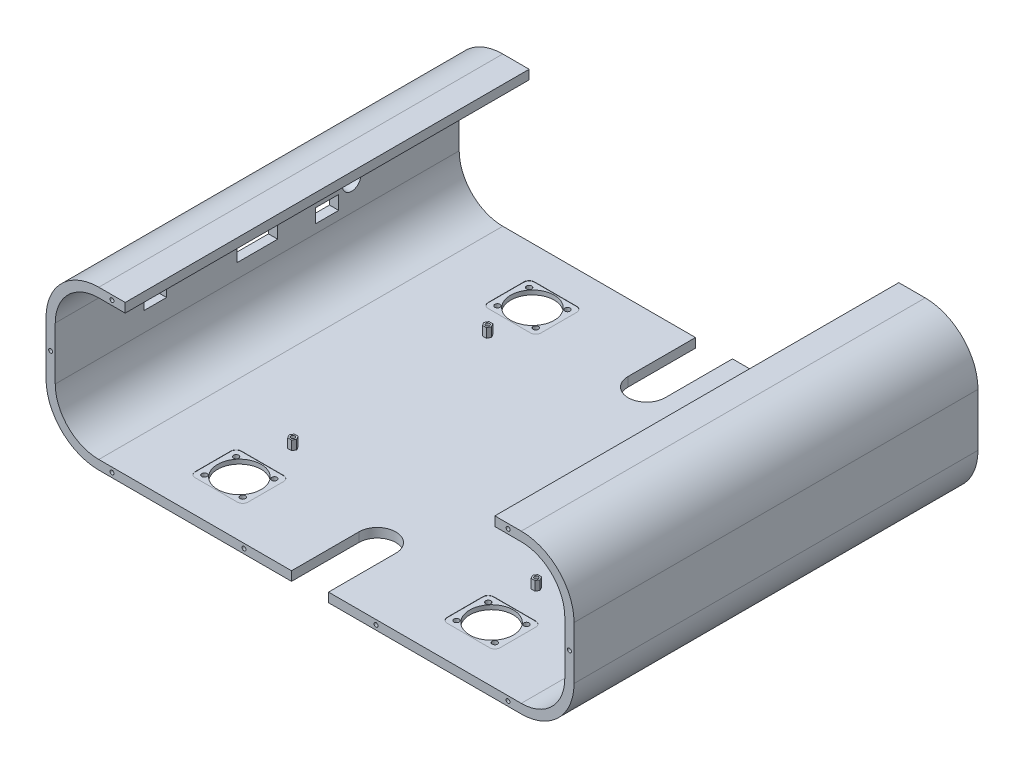
SolidWorks part; units mm, degrees
material "6061-T6 (SS)"
ref_plane "Front Plane" through (0, 0, 0) normal (0, 0, 1) x (1, 0, 0)
ref_plane "Top Plane" through (0, 0, 0) normal (0, 1, 0) x (1, 0, 0)
ref_plane "Right Plane" through (0, 0, 0) normal (1, 0, 0) x (0, 0, -1)
sketch "Sketch1" plane through (0, 0, 0) normal (0, 1, 0) x (1, 0, 0)
  line L1 (-200, -153) -> (200, -153)
  line L2 (-200, -153) -> (-200, 153)
  line L3 (-200, 153) -> (200, 153)
  line L4 (200, -153) -> (200, 153)
  line L5 (-200, -153) -> (200, 153) construction
  line L6 (-200, 153) -> (200, -153) construction
  point P0 (0, 0)
  dimension "D1" = 400
  dimension "D2" = 306
extrude "Boss-Extrude1" add sketch "Sketch1" along normal blind 7
sketch "Sketch5" plane through (0, 0, 153) normal (0, 0, 1) x (1, 0, 0)
  line L0 (0, 0) -> (0, 120) construction
  line L1 (-140, 0) -> (-160, 0)
  line L3 (-200, 0) -> (200, 0) construction
  line L17 (-200, 40) -> (-200, 80)
  line L20 (-200, 120) -> (-200, 0) construction
  line L21 (-140, 120) -> (-160, 120)
  line L22 (-140, 113) -> (-160, 113)
  line L24 (-193, 40) -> (-193, 80)
  line L25 (-140, 7) -> (-160, 7)
  line L26 (-140, 113) -> (-140, 120)
  line L27 (-140, 0) -> (-140, 7)
  line L28 (200, 120) -> (200, 0) construction
  line L29 (140, 0) -> (140, 7)
  line L30 (140, 113) -> (140, 120)
  line L31 (140, 7) -> (160, 7)
  line L32 (193, 40) -> (193, 80)
  line L33 (-200, 60) -> (200, 60) construction
  line L34 (140, 113) -> (160, 113)
  line L35 (140, 120) -> (160, 120)
  line L36 (200, 40) -> (200, 80)
  line L37 (140, 0) -> (160, 0)
  arc A0 (-160, 0) -> (-200, 40) centre (-160, 40) cw
  arc A3 (-160, 120) -> (-200, 80) centre (-160, 80) ccw
  arc A4 (-160, 113) -> (-193, 80) centre (-160, 80) ccw
  arc A5 (-160, 7) -> (-193, 40) centre (-160, 40) cw
  arc A6 (160, 7) -> (193, 40) centre (160, 40) ccw
  arc A7 (160, 113) -> (193, 80) centre (160, 80) cw
  arc A8 (160, 120) -> (200, 80) centre (160, 80) cw
  arc A9 (160, 0) -> (200, 40) centre (160, 40) ccw
  point P3 (0, 60)
  dimension "D1" = 60
  dimension "D2" = 20
  dimension "D3" = 20
  dimension "D4" = 120
  dimension "D5" = 7
extrude "Boss-Extrude3" add sketch "Sketch5" against normal up to surface (306 mm away) up to face at (0, 3.5, -153)
sketch "Sketch6" plane through (0, 0, 153) normal (0, 0, 1) x (1, 0, 0)
  line L8 (-182.6053, 7) -> (-200, 7)
  line L9 (-200, 7) -> (-200, 0)
  line L10 (-200, 0) -> (-160, 0)
  line L11 (0, -55) -> (0, 55) construction
  line L12 (200, 0) -> (160, 0)
  line L13 (200, 7) -> (200, 0)
  line L14 (182.6053, 7) -> (200, 7)
  arc A3 (-200, 40) -> (-160, 0) centre (-160, 40) ccw construction
  arc A4 (-182.6053, 7) -> (-160, 0) centre (-160, 40) ccw
  arc A5 (182.6053, 7) -> (160, 0) centre (160, 40) cw
extrude "Cut-Extrude1" cut sketch "Sketch6" against normal through all both and the other way through all
sketch "Sketch7" plane through (0, 0, 153) normal (0, 0, 1) x (1, 0, 0)
  line L0 (0, 7) -> (0, 0) construction
  line L1 (-160, 7) -> (160, 7) construction
  line L2 (-160, 0) -> (160, 0) construction
  line L3 (-193, 40) -> (-193, 80) construction
  circle A0 centre (-50, 3.5) radius 1.5
  circle A1 centre (-150, 3.5) radius 1.5
  circle A2 centre (-196.5, 60) radius 1.5
  circle A3 centre (-150, 116.5) radius 1.5
  circle A4 centre (150, 116.5) radius 1.5
  circle A5 centre (196.5, 60) radius 1.5
  circle A6 centre (150, 3.5) radius 1.5
  circle A7 centre (50, 3.5) radius 1.5
  dimension "D1" = 3
  dimension "D2" = 50
  dimension "D3" = 3
  dimension "D4" = 100
  dimension "D5" = 3
  dimension "D6" = 3.5
  dimension "D7" = 60
  dimension "D8" = 3
extrude "Cut-Extrude2" cut sketch "Sketch7" against normal blind 7 and the other way through all
mirror "Mirror1" about plane through (0, 0, 0) normal (0, 0, 1) of "Cut-Extrude2"
sketch "Sketch8" plane through (0, 7, 0) normal (0, 1, 0) x (1, 0, 0)
  line L0 (-160, -153) -> (160, -153) construction
  line L1 (-14, -218) -> (14, -218)
  line L2 (-14, -218) -> (-14, -88)
  line L3 (-14, -88) -> (14, -88)
  line L4 (14, -218) -> (14, -88)
  line L5 (-14, -218) -> (14, -88) construction
  line L6 (-14, -88) -> (14, -218) construction
  line L7 (-66, 0) -> (66, 0) construction
  line L8 (-14, 218) -> (14, 218)
  line L9 (-14, 88) -> (14, 218) construction
  line L10 (-14, 218) -> (14, 88) construction
  line L11 (14, 218) -> (14, 88)
  line L12 (-14, 88) -> (14, 88)
  line L13 (-14, 218) -> (-14, 88)
  point P0 (0, -153)
  point P13 (0, 153)
  dimension "D1" = 28
  dimension "D2" = 130
extrude "Cut-Extrude3" cut sketch "Sketch8" against normal through all both and the other way through all
fillet "Fillet1" radius 14 4 edges at (0, 7, 88) (-14, 3.5, 88) (0, 0, 88) (14, 3.5, 88)
fillet "Fillet2" radius 14 4 edges at (0, 7, -88) (14, 3.5, -88) (0, 0, -88) (-14, 3.5, -88)
sketch "Sketch9" plane through (0, 7, 0) normal (0, 1, 0) x (1, 0, 0)
  line L0 (-66, 0) -> (66, 0) construction
  line L5 (100, -80) -> (-100, 80) construction
  line L6 (100, 80) -> (-100, -80) construction
  line L7 (-89.3046, 73.753) -> (-90.7479, 76.253)
  line L8 (-90.7479, 76.253) -> (-93.6347, 76.253)
  line L9 (-93.6347, 76.253) -> (-95.0781, 73.753)
  line L10 (-95.0781, 73.753) -> (-93.6347, 71.253)
  line L11 (-93.6347, 71.253) -> (-90.7479, 71.253)
  line L12 (-90.7479, 71.253) -> (-89.3046, 73.753)
  line L13 (-90.7479, -71.253) -> (-89.3046, -73.753)
  line L14 (-93.6347, -71.253) -> (-90.7479, -71.253)
  line L15 (-95.0781, -73.753) -> (-93.6347, -71.253)
  line L16 (-93.6347, -76.253) -> (-95.0781, -73.753)
  line L17 (-90.7479, -76.253) -> (-93.6347, -76.253)
  line L18 (-89.3046, -73.753) -> (-90.7479, -76.253)
  line L19 (0, -66) -> (0, 66) construction
  line L20 (-100, 80) -> (100, -80) construction
  line L21 (-100, -80) -> (100, 80) construction
  line L22 (89.3046, -73.753) -> (90.7479, -76.253)
  line L23 (90.7479, -76.253) -> (93.6347, -76.253)
  line L24 (93.6347, -76.253) -> (95.0781, -73.753)
  line L25 (95.0781, -73.753) -> (93.6347, -71.253)
  line L26 (93.6347, -71.253) -> (90.7479, -71.253)
  line L27 (90.7479, -71.253) -> (89.3046, -73.753)
  line L28 (90.7479, 71.253) -> (89.3046, 73.753)
  line L29 (93.6347, 71.253) -> (90.7479, 71.253)
  line L30 (95.0781, 73.753) -> (93.6347, 71.253)
  line L31 (93.6347, 76.253) -> (95.0781, 73.753)
  line L32 (90.7479, 76.253) -> (93.6347, 76.253)
  line L33 (89.3046, 73.753) -> (90.7479, 76.253)
  circle A0 centre (-92.1913, 73.753) radius 2.5 construction
  circle A1 centre (-92.1913, 73.753) radius 1.5
  circle A2 centre (-92.1913, -73.753) radius 2.5 construction
  circle A3 centre (-92.1913, -73.753) radius 1.5
  circle A4 centre (92.1913, -73.753) radius 2.5 construction
  circle A5 centre (92.1913, 73.753) radius 2.5 construction
  circle A6 centre (92.1913, -73.753) radius 1.5
  circle A7 centre (92.1913, 73.753) radius 1.5
  point P0 (0, 0)
  dimension "D3" = 5
  dimension "D4" = 3
  dimension "D1" = 160
  dimension "D2" = 200
  dimension "D5" = 10
extrude "Boss-Extrude4" add sketch "Sketch9" along normal blind 7 from offset 2 separate body
sketch "Sketch10" plane through (0, 0, 0) normal (0, -1, 0) x (1, 0, 0)
  line L0 (-160, -153) -> (-160, 153) construction
  line L1 (-160, 153) -> (-14, 153) construction
  line L2 (66, 0) -> (-66, 0) construction
  line L3 (0, -66) -> (0, 66) construction
  line L4 (-110, 123) -> (-81, 99) construction
  line L5 (-81, 99) -> (-81, 123) construction
  line L6 (-81, 123) -> (-110, 99) construction
  line L7 (-110, 99) -> (-110, 123) construction
  line L8 (-110, 123) -> (-81, 123) construction
  circle A0 centre (-110, 123) radius 2
  circle A1 centre (-81, 123) radius 2
  circle A2 centre (0, 0) radius 2
  circle A3 centre (0, 0) radius 2
  circle A4 centre (-110, 99) radius 2
  circle A5 centre (-81, 99) radius 2
  circle A6 centre (-81, -99) radius 2
  circle A7 centre (-110, -99) radius 2
  circle A8 centre (-81, -123) radius 2
  circle A9 centre (-110, -123) radius 2
  circle A10 centre (110, -123) radius 2
  circle A11 centre (81, -123) radius 2
  circle A12 centre (110, -99) radius 2
  circle A13 centre (81, -99) radius 2
  circle A14 centre (81, 99) radius 2
  circle A15 centre (110, 99) radius 2
  circle A16 centre (81, 123) radius 2
  circle A17 centre (110, 123) radius 2
  circle A18 centre (-95.5, 111) radius 16.5
  circle A19 centre (95.5, 111) radius 16.5
  circle A20 centre (95.5, -111) radius 16.5
  circle A21 centre (-95.5, -111) radius 16.5
  dimension "D1" = 4
  dimension "D2" = 4
  dimension "D3" = 4
  dimension "D4" = 4
  dimension "D5" = 4
  dimension "D6" = 29
  dimension "D7" = 24
  dimension "D10" = 33
  dimension "D13" = 33
  dimension "D8" = 50
  dimension "D9" = 30
  dimension "D11" = 14.5
  dimension "D12" = 12
extrude "Cut-Extrude4" cut sketch "Sketch10" against normal through all both and the other way through all contours A0 | A4 | A1 | A5 | A9 | A7 | A8 | A6 | A11 | A12 | A10 | A13 | A15 | A14 | A16 | A17 | A18 | A21 | A20 | A19
sketch "Sketch12" plane through (0, 0, 0) normal (0, -1, 0) x (1, 0, 0)
  line L0 (66, 0) -> (-66, 0) construction
  line L1 (0, -66) -> (0, 66) construction
  circle A0 centre (-95.5, 111) radius 30
  circle A1 centre (-95.5, -111) radius 30
  circle A2 centre (95.5, -111) radius 30
  circle A3 centre (95.5, 111) radius 30
  dimension "D1" = 60
extrude "Cut-Extrude5" cut sketch "Sketch12" against normal blind 3.5 and the other way through all
sketch "Sketch13" plane through (0, 7, 0) normal (0, 1, 0) x (1, 0, 0)
  line L0 (0, -66) -> (0, 66) construction
  line L1 (-115.5, -128.5) -> (-75.5, -128.5)
  line L2 (-115.5, -128.5) -> (-115.5, -93.5)
  line L3 (-115.5, -93.5) -> (-75.5, -93.5)
  line L4 (-75.5, -128.5) -> (-75.5, -93.5)
  line L5 (-115.5, -128.5) -> (-75.5, -93.5) construction
  line L6 (-115.5, -93.5) -> (-75.5, -128.5) construction
  line L7 (115.5, -93.5) -> (75.5, -128.5) construction
  line L8 (115.5, -128.5) -> (75.5, -93.5) construction
  line L9 (115.5, -93.5) -> (75.5, -93.5)
  line L10 (115.5, -128.5) -> (115.5, -93.5)
  line L11 (115.5, -128.5) -> (75.5, -128.5)
  line L12 (75.5, -128.5) -> (75.5, -93.5)
  line L13 (-66, 0) -> (66, 0) construction
  line L14 (115.5, 128.5) -> (75.5, 93.5) construction
  line L15 (115.5, 93.5) -> (75.5, 128.5) construction
  line L16 (-115.5, 93.5) -> (-75.5, 128.5) construction
  line L17 (-115.5, 128.5) -> (-75.5, 93.5) construction
  line L18 (75.5, 128.5) -> (75.5, 93.5)
  line L19 (115.5, 128.5) -> (75.5, 128.5)
  line L20 (115.5, 128.5) -> (115.5, 93.5)
  line L21 (115.5, 93.5) -> (75.5, 93.5)
  line L22 (-75.5, 128.5) -> (-75.5, 93.5)
  line L23 (-115.5, 93.5) -> (-75.5, 93.5)
  line L24 (-115.5, 128.5) -> (-115.5, 93.5)
  line L25 (-115.5, 128.5) -> (-75.5, 128.5)
  point P0 (-95.5, -111)
  point P12 (95.5, -111)
  point P23 (95.5, 111)
  point P24 (-95.5, 111)
  dimension "D1" = 40
  dimension "D2" = 35
extrude "Cut-Extrude6" cut sketch "Sketch13" against normal blind 0.2
fillet "Fillet3" radius 4 16 edges at (75.5, 6.9, -128.5) (75.5, 6.9, -93.5) (115.5, 6.9, -93.5) (115.5, 6.9, -128.5) (-75.5, 6.9, -128.5) (-115.5, 6.9, -128.5) (-75.5, 6.9, -93.5) (-115.5, 6.9, -93.5) (-75.5, 6.9, 128.5) (-75.5, 6.9, 93.5) (-115.5, 6.9, 128.5) (-115.5, 6.9, 93.5) (75.5, 6.9, 93.5) (115.5, 6.9, 93.5) (75.5, 6.9, 128.5) (115.5, 6.9, 128.5)
sketch "Sketch16" plane through (-200, 0, 0) normal (-1, 0, 0) x (0, 0, 1)
  line L0 (-153, 61.5) -> (153, 60) construction
  line L1 (153, 40) -> (153, 80) construction
  line L2 (0, 0) -> (0, 80) construction
  line L3 (-153, 80) -> (153, 80) construction
  line L5 (-15.5, 50.75) -> (15.5, 50.75)
  line L6 (-15.5, 50.75) -> (-15.5, 70.75)
  line L7 (-15.5, 70.75) -> (15.5, 70.75)
  line L8 (15.5, 50.75) -> (15.5, 70.75)
  line L9 (-15.5, 50.75) -> (15.5, 70.75) construction
  line L10 (-15.5, 70.75) -> (15.5, 50.75) construction
  line L11 (-59.1, 67.5099) -> (-46.9, 67.5099)
  line L12 (-59.1, 67.5099) -> (-59.1, 73.0099)
  line L13 (-59.1, 73.0099) -> (-46.9, 73.0099)
  line L14 (-46.9, 67.5099) -> (-46.9, 73.0099)
  line L15 (-59.1, 67.5099) -> (-46.9, 73.0099) construction
  line L16 (-59.1, 73.0099) -> (-46.9, 67.5099) construction
  line L17 (-61.75, 46.5099) -> (-44.25, 46.5099)
  line L18 (-61.75, 46.5099) -> (-61.75, 57.0099)
  line L19 (-61.75, 57.0099) -> (-44.25, 57.0099)
  line L20 (-44.25, 46.5099) -> (-44.25, 57.0099)
  line L21 (-61.75, 46.5099) -> (-44.25, 57.0099) construction
  line L22 (-61.75, 57.0099) -> (-44.25, 46.5099) construction
  line L27 (68.6449, 54.5711) -> (85.9449, 54.5711)
  line L28 (68.6449, 54.5711) -> (68.6449, 66.1711)
  line L29 (68.6449, 66.1711) -> (85.9449, 66.1711)
  line L30 (85.9449, 54.5711) -> (85.9449, 66.1711)
  line L31 (68.6449, 54.5711) -> (85.9449, 66.1711) construction
  line L32 (68.6449, 66.1711) -> (85.9449, 54.5711) construction
  circle A0 centre (-71.5, 61.1005) radius 6.93
  point P10 (0, 60.75)
  point P15 (-53, 70.2599)
  point P20 (-53, 51.7599)
  point P25 (77.2949, 60.3711)
  dimension "D10" = 13.86
  dimension "D11" = 100
  dimension "D1" = 31
  dimension "D2" = 20
  dimension "D3" = 18.5
  dimension "D4" = 9.25
  dimension "D5" = 18.5
  dimension "D6" = 10.5
  dimension "D7" = 17.5
  dimension "D8" = 12.2
  dimension "D9" = 5.5
  dimension "D12" = 18.5
  dimension "D13" = 17.3
  dimension "D14" = 11.6
extrude "Cut-Extrude7" cut sketch "Sketch16" against normal blind 10
